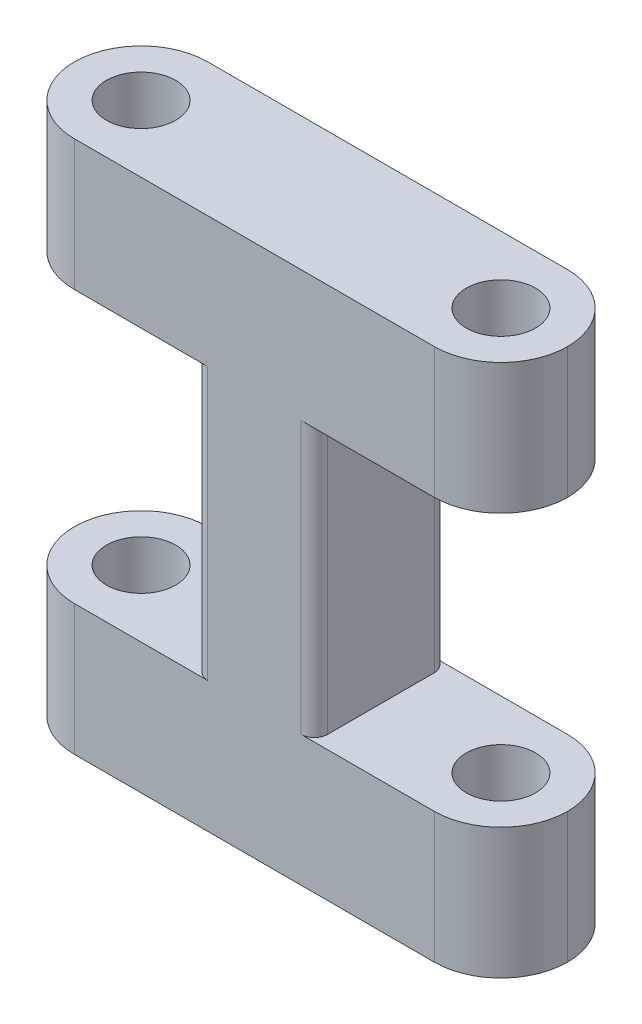
SolidWorks part; units mm, degrees
ref_plane "Front Plane" through (0, 0, 0) normal (0, 0, 1) x (1, 0, 0)
ref_plane "Top Plane" through (0, 0, 0) normal (0, 1, 0) x (1, 0, 0)
ref_plane "Right Plane" through (0, 0, 0) normal (1, 0, 0) x (0, 0, -1)
sketch "Sketch1" plane through (0, 0, 0) normal (0, 0, 1) x (1, 0, 0)
  line L0 (-18.5, 0) -> (18.5, 0) construction
  line L1 (-18.5, -20) -> (18.5, -20)
  line L2 (-18.5, -20) -> (-18.5, 20)
  line L3 (-18.5, 20) -> (18.5, 20)
  line L4 (18.5, -20) -> (18.5, 20)
  line L5 (-18.5, -20) -> (18.5, 20) construction
  line L6 (-18.5, 20) -> (18.5, -20) construction
  line L8 (-32.5, -10.2) -> (-4.5, -10.2)
  line L9 (-32.5, -10.2) -> (-32.5, 10.2)
  line L10 (-32.5, 10.2) -> (-4.5, 10.2)
  line L11 (-4.5, -10.2) -> (-4.5, 10.2)
  line L12 (-32.5, -10.2) -> (-4.5, 10.2) construction
  line L13 (-32.5, 10.2) -> (-4.5, -10.2) construction
  line L14 (32.5, -10.2) -> (4.5, -10.2)
  line L15 (32.5, -10.2) -> (32.5, 10.2)
  line L16 (32.5, 10.2) -> (4.5, 10.2)
  line L17 (4.5, -10.2) -> (4.5, 10.2)
  line L18 (32.5, -10.2) -> (4.5, 10.2) construction
  line L19 (32.5, 10.2) -> (4.5, -10.2) construction
  point P0 (0, 0)
  dimension "D1" = 37
  dimension "D2" = 40
  dimension "D3" = 20.4
  dimension "D4" = 20.4
  dimension "D5" = 28
  dimension "D6" = 28
extrude "Boss-Extrude2" add sketch "Sketch1" along normal blind 10 contours L14 L17 L16 L4 L3 L2 L10 L11 L8 L1 region at (0, 0, 0)
fillet "Fillet1" radius 5 8 edges at (18.5, 15.1, 0) (18.5, 15.1, 10) (18.5, -15.1, 0) (18.5, -15.1, 10) (-18.5, 15.1, 0) (-18.5, -15.1, 0) (-18.5, -15.1, 10) (-18.5, 15.1, 10)
fillet "Fillet2" radius 1 4 edges at (4.5, 0, 0) (4.5, 0, 10) (-4.5, 0, 0) (-4.5, 0, 10)
sketch "Sketch2" plane through (0, -20, 0) normal (0, -1, 0) x (1, 0, 0)
  circle A0 centre (-13.5, 5) radius 2.6
  circle A1 centre (13.5, 5) radius 2.6
  dimension "D1" = 5.2
  dimension "D2" = 5.2
extrude "Cut-Extrude1" cut sketch "Sketch2" against normal through all
